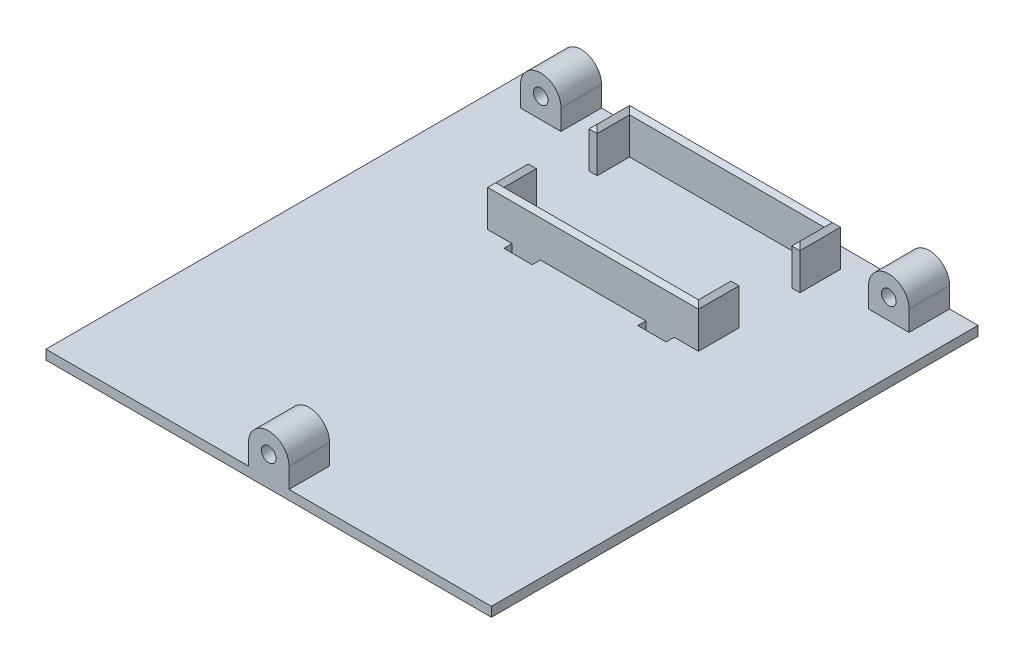
SolidWorks part; units mm, degrees
ref_plane "Front Plane" through (0, 0, 0) normal (0, 0, 1) x (1, 0, 0)
ref_plane "Top Plane" through (0, 0, 0) normal (0, 1, 0) x (1, 0, 0)
ref_plane "Right Plane" through (0, 0, 0) normal (1, 0, 0) x (0, 0, -1)
sketch "Sketch1" plane through (0, 0, 0) normal (0, 1, 0) x (1, 0, 0)
  line L1 (0, 0) -> (139.5, 0)
  line L2 (0, 0) -> (0, 152.4)
  line L3 (0, 152.4) -> (139.5, 152.4)
  line L4 (139.5, 0) -> (139.5, 152.4)
  dimension "D1" = 152.4
  dimension "D2" = 139.5
extrude "Boss-Extrude1" add sketch "Sketch1" along normal blind 6.35
sketch "Sketch2" plane through (0, 6.35, 0) normal (0, 1, 0) x (1, 0, 0)
  line L0 (0, 0) -> (139.5, 0) construction
  line L1 (0, 152.4) -> (139.5, 152.4)
  line L2 (0, 152.4) -> (0, 0)
  line L3 (0, 0) -> (139.5, 0)
  line L4 (139.5, 152.4) -> (139.5, 0)
  line L5 (139.5, 0) -> (139.5, 152.4) construction
extrude "Cut-Extrude1" cut sketch "Sketch2" against normal blind 3.375
sketch "Sketch3" plane through (0, 0, 0) normal (0, 0, 1) x (1, 0, 0)
  line L0 (63.4, 9.325) -> (63.4, 2.975)
  line L1 (63.4, 2.975) -> (76.1, 2.975)
  line L2 (76.1, 9.325) -> (76.1, 2.975)
  line L3 (0, 2.975) -> (139.5, 2.975) construction
  arc A0 (76.1, 9.325) -> (63.4, 9.325) centre (69.75, 9.325) ccw
  circle A1 centre (69.75, 9.325) radius 2.286
  point P6 (69.75, 2.975)
  point P9 (69.75, 2.975)
  dimension "D1" = 4.572
  dimension "D2" = 12.7
  dimension "D8" = 6.35
  dimension "D5" = 6.35
extrude "Boss-Extrude2" add sketch "Sketch3" against normal blind 12.7
sketch "Sketch4" plane through (0, 0, -152.4) normal (0, 0, -1) x (-1, 0, 0)
  line L0 (-130.61, 9.325) -> (-130.61, 2.975)
  line L1 (-130.61, 2.975) -> (-117.91, 2.975)
  line L2 (-117.91, 9.325) -> (-117.91, 2.975)
  line L3 (-21.59, 9.325) -> (-21.59, 2.975)
  line L4 (-21.59, 2.975) -> (-8.89, 2.975)
  line L5 (-8.89, 9.325) -> (-8.89, 2.975)
  line L6 (-139.5, 2.975) -> (0, 2.975) construction
  line L7 (0, 2.975) -> (0, 0) construction
  line L8 (-139.5, 2.975) -> (-139.5, 0) construction
  arc A0 (-117.91, 9.325) -> (-130.61, 9.325) centre (-124.26, 9.325) ccw
  circle A1 centre (-124.26, 9.325) radius 2.286
  arc A2 (-8.89, 9.325) -> (-21.59, 9.325) centre (-15.24, 9.325) ccw
  circle A3 centre (-15.24, 9.325) radius 2.286
  dimension "D1" = 4.572
  dimension "D3" = 6.35
  dimension "D5" = 4.572
  dimension "D7" = 6.35
  dimension "D2" = 6.35
  dimension "D4" = 12.7
  dimension "D6" = 6.35
  dimension "D8" = 12.7
  dimension "D9" = 8.89
  dimension "D10" = 8.89
  dimension "D11" = 15.24
  dimension "D12" = 15.24
extrude "Boss-Extrude3" add sketch "Sketch4" against normal blind 12.7
sketch "Sketch5" plane through (0, 2.975, 0) normal (0, 1, 0) x (1, 0, 0)
  line L0 (36.73, 146.05) -> (36.73, 133.35)
  line L1 (39.27, 143.51) -> (100.23, 143.51)
  line L2 (39.27, 143.51) -> (39.27, 133.35)
  line L3 (39.27, 104.14) -> (100.23, 104.14)
  line L4 (100.23, 143.51) -> (100.23, 133.35)
  line L5 (36.73, 101.6) -> (102.77, 101.6)
  line L6 (102.77, 146.05) -> (102.77, 133.35)
  line L7 (36.73, 146.05) -> (102.77, 146.05)
  line L8 (117.91, 152.4) -> (21.59, 152.4) construction
  line L9 (36.73, 133.35) -> (39.27, 133.35)
  line L10 (36.73, 114.3) -> (39.27, 114.3)
  line L11 (100.23, 114.3) -> (102.77, 114.3)
  line L12 (100.23, 133.35) -> (102.77, 133.35)
  line L13 (39.27, 114.3) -> (39.27, 104.14)
  line L14 (39.27, 143.51) -> (39.27, 104.14) construction
  line L15 (36.73, 114.3) -> (36.73, 101.6)
  line L16 (36.73, 146.05) -> (36.73, 101.6) construction
  line L17 (100.23, 114.3) -> (100.23, 104.14)
  line L18 (100.23, 143.51) -> (100.23, 104.14) construction
  line L19 (102.77, 114.3) -> (102.77, 101.6)
  line L20 (102.77, 146.05) -> (102.77, 101.6) construction
  point P8 (69.75, 146.05)
  point P11 (69.75, 152.4)
  dimension "D1" = 60.96
  dimension "D2" = 39.37
  dimension "D4" = 6.35
  dimension "D5" = 12.7
  dimension "D3" = 2.54
extrude "Boss-Extrude4" add sketch "Sketch5" along normal blind 12.7
chamfer "Chamfer1" distance 1.27 angle 45 16 edges at (101.5, 15.675, -114.3) (102.77, 15.675, -107.95) (69.75, 15.675, -101.6) (36.73, 15.675, -107.95) (38, 15.675, -114.3) (39.27, 15.675, -109.22) (69.75, 15.675, -104.14) (100.23, 15.675, -109.22) (38, 15.675, -133.35) (36.73, 15.675, -139.7) (69.75, 15.675, -146.05) (102.77, 15.675, -139.7) (101.5, 15.675, -133.35) (100.23, 15.675, -138.43) (69.75, 15.675, -143.51) (39.27, 15.675, -138.43)
sketch "Sketch6" plane through (0, 2.975, 0) normal (0, 1, 0) x (1, 0, 0)
  line L0 (102.77, 146.05) -> (36.73, 146.05) construction
  line L1 (44.35, 146.05) -> (53.24, 146.05)
  line L2 (44.35, 146.05) -> (44.35, 148.59)
  line L3 (44.35, 148.59) -> (53.24, 148.59)
  line L4 (53.24, 146.05) -> (53.24, 148.59)
  line L5 (102.77, 101.6) -> (36.73, 101.6) construction
  line L6 (86.26, 146.05) -> (95.15, 146.05)
  line L7 (86.26, 146.05) -> (86.26, 148.59)
  line L8 (86.26, 148.59) -> (95.15, 148.59)
  line L9 (95.15, 146.05) -> (95.15, 148.59)
  line L10 (44.35, 101.6) -> (53.24, 101.6)
  line L11 (44.35, 101.6) -> (44.35, 99.06)
  line L12 (44.35, 99.06) -> (53.24, 99.06)
  line L13 (53.24, 101.6) -> (53.24, 99.06)
  line L14 (36.73, 114.3) -> (36.73, 101.6) construction
  line L15 (86.26, 101.6) -> (95.15, 101.6)
  line L16 (86.26, 101.6) -> (86.26, 99.06)
  line L17 (86.26, 99.06) -> (95.15, 99.06)
  line L18 (95.15, 101.6) -> (95.15, 99.06)
  line L19 (36.73, 133.35) -> (36.73, 146.05) construction
  line L20 (102.77, 114.3) -> (102.77, 101.6) construction
  line L21 (102.77, 146.05) -> (102.77, 133.35) construction
  dimension "D1" = 8.89
  dimension "D2" = 2.54
  dimension "D3" = 7.62
  dimension "D4" = 7.62
  dimension "D5" = 7.62
  dimension "D6" = 7.62
extrude "Cut-Extrude2" cut sketch "Sketch6" against normal through all
